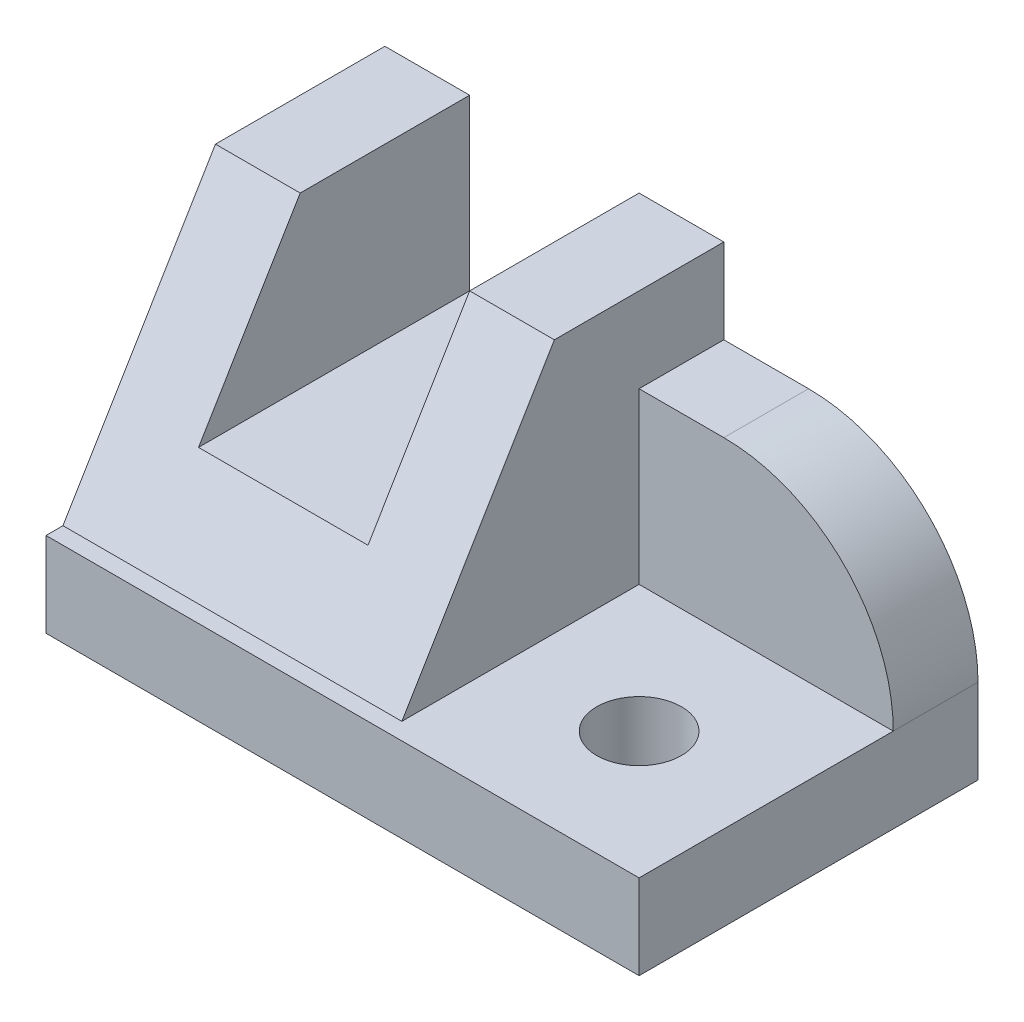
SolidWorks part; units mm, degrees
ref_plane "Front Plane" through (0, 0, 0) normal (0, 0, 1) x (1, 0, 0)
ref_plane "Top Plane" through (0, 0, 0) normal (0, 1, 0) x (1, 0, 0)
ref_plane "Right Plane" through (0, 0, 0) normal (1, 0, 0) x (0, 0, -1)
ref_plane "Plane1" through (0, 0, 0) normal (-1, 0, 0) x (0, -1, 0)
sketch "Sketch1" plane through (0, 0, 0) normal (-1, 0, 0) x (0, -1, 0)
  line L0 (-10, -2) -> (-40, -20)
  line L1 (-40, -20) -> (-10, -20)
  line L2 (-10, -20) -> (-10, -2)
  dimension "D1" = 30
  dimension "Width" = 18
extrude "Boss-Extrude1" add sketch "Sketch1" against normal blind 40
sketch "Sketch2" plane through (0, 0, -20) normal (0, 0, -1) x (-1, 0, 0)
  line L0 (-40, 40) -> (0, 40)
  line L1 (0, 40) -> (0, 10)
  line L2 (0, 10) -> (-40, 10)
  line L3 (-40, 10) -> (-40, 40)
extrude "Boss-Extrude2" add sketch "Sketch2" along normal blind 20
sketch "Sketch3" plane through (40, 0, 0) normal (1, 0, 0) x (0, 0, -1)
  line L0 (40, 10) -> (0, 10)
  line L1 (0, 10) -> (20, 40)
  line L2 (20, 40) -> (40, 40)
  line L3 (40, 40) -> (40, 10)
extrude "Boss-Extrude3" add sketch "Sketch3" along normal blind 30
sketch "Sketch4" plane through (70, 0, 0) normal (1, 0, 0) x (0, 0, -1)
  line L0 (20, 40) -> (0, 10)
  line L1 (0, 10) -> (30, 10)
  line L2 (30, 10) -> (30, 30)
  line L3 (30, 30) -> (40, 30)
  line L4 (40, 30) -> (40, 40)
  line L5 (40, 40) -> (20, 40)
extrude "Cut-Extrude1" cut sketch "Sketch4" against normal blind 30
sketch "Sketch5" plane through (0, 10, 0) normal (0, -1, 0) x (1, 0, 0)
  line L0 (70, 0) -> (70, -40)
  line L1 (70, -40) -> (0, -40)
  line L2 (0, -40) -> (0, 0)
  line L3 (0, 0) -> (70, 0)
extrude "Boss-Extrude4" add sketch "Sketch5" along normal blind 10
sketch "Sketch6" plane through (0, 0, -40) normal (0, 0, -1) x (-1, 0, 0)
  line L0 (-30, 40) -> (-30, 20)
  line L1 (-30, 20) -> (-10, 20)
  line L2 (-10, 20) -> (-10, 40)
  line L3 (-10, 40) -> (-30, 40)
extrude "Cut-Extrude2" cut sketch "Sketch6" against normal through all
hole_wizard "Ø10.0 (10) Diameter Hole1" positions "Sketch8" profile "Sketch7" hole size "Ø10.0" standard "ANSI Metric"
sketch "Sketch8" plane through (0, 0, 0) normal (0, -1, 0) x (-1, 0, 0)
  point P0 (-55, 15)
sketch "Sketch7" plane through (55, 0, -15) normal (1, 0, 0) x (0, 0, -1)
  line L0 (0, 0) -> (0, 40)
  line L1 (0, 40) -> (5, 40)
  line L2 (5, 40) -> (5, 0)
  line L5 (5, 0) -> (0, 0)
  line L11 (0, -6.35) -> (0, 107.95) construction
  dimension "Thru Hole Dia." = 10
  dimension "Thru Hole Depth" = 40
fillet "Fillet1" radius 20 1 edges at (70, 30, -35) tangent propagation no
